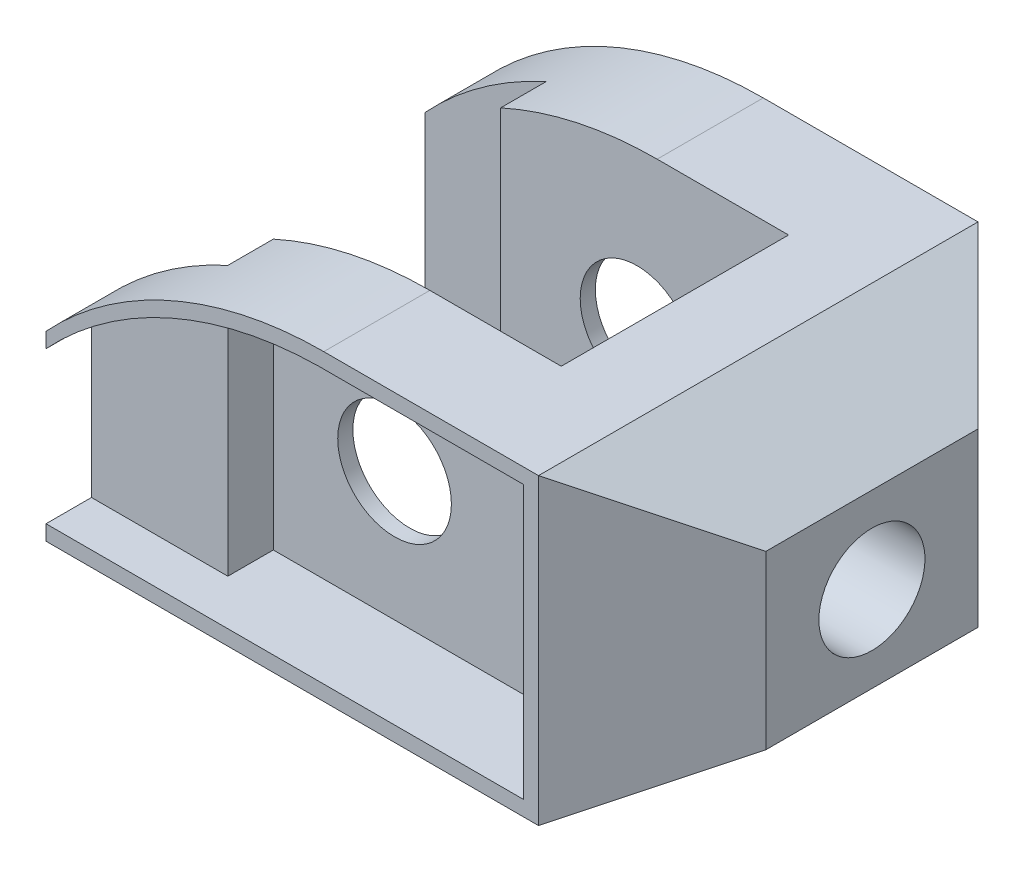
SolidWorks part; units mm, degrees
material "1060 Alloy"
ref_plane "Front Plane" through (0, 0, 0) normal (0, 0, 1) x (1, 0, 0)
ref_plane "Top Plane" through (0, 0, 0) normal (0, 1, 0) x (1, 0, 0)
ref_plane "Right Plane" through (0, 0, 0) normal (1, 0, 0) x (0, 0, -1)
sketch "Sketch2" plane through (0, 0, 0) normal (0, 1, 0) x (1, 0, 0)
  line L0 (0, 71.5823) -> (0, -71.5823) construction
  line L1 (-112.3291, 0) -> (112.3291, 0) construction
  line L3 (-40, 29) -> (40, 29)
  line L4 (-40, 29) -> (-40, -29)
  line L5 (-40, -29) -> (40, -29)
  line L6 (40, 29) -> (40, -29)
  point P0 (0, 0)
  point P4 (0, 0)
  point P8 (0, 0)
  dimension "D1" = 58
  dimension "D2" = 80
extrude "Boss-Extrude1" add sketch "Sketch2" along normal blind 40
sketch "Sketch4" plane through (0, 0, 0) normal (0, 0, 1) x (1, 0, 0)
  line L0 (40, 0) -> (25, 0)
  line L1 (-40, 0) -> (40, 0) construction
  line L2 (25, 0) -> (40, 8.6603)
  line L3 (40, 40) -> (40, 0) construction
  line L4 (40, 40) -> (25, 40)
  line L5 (-40, 40) -> (40, 40) construction
  line L6 (25, 40) -> (40, 31.3397)
  line L7 (-40, 0) -> (-40, 24)
  line L8 (-40, 40) -> (-40, 0) construction
  line L9 (25, 40) -> (-6, 40)
  line L10 (-6, 40) -> (-40, 40)
  line L11 (-40, 40) -> (-40, 24)
  line L12 (40, 40) -> (40, 0)
  line L13 (-40, 0) -> (40, 0)
  circle A0 centre (-6, 19) radius 7.5
  arc A2 (-3.3394, 40) -> (-40, 24) centre (-3.3394, -10) ccw
  dimension "D1" = 15
  dimension "D9" = 100
  dimension "D2" = 19
  dimension "D3" = 46
  dimension "D4" = 30
  dimension "D5" = 15
  dimension "D6" = 15
  dimension "D7" = 30
  dimension "D8" = 24
  dimension "D10" = 31
extrude "Cut-Extrude7" cut sketch "Sketch4" against normal blind 58 and the other way blind 58 contours A2 L9 L10 L11 | L12 L4 L6 | A0 | L12 L2 L0 region at (35, 2.8868, 0) region at (35, 37.1132, 0) region at (-31.154, 35.3681, 0) region at (-6, 19, 0)
sketch "Sketch12" plane through (0, 40, 0) normal (0, 1, 0) x (1, 0, 0)
  line L0 (14, 29) -> (14, -29)
  line L1 (25, 29) -> (-3.3394, 29) construction
  line L2 (-3.3394, -29) -> (25, -29) construction
  line L3 (25, -29) -> (25, 29) construction
  line L4 (14, 15) -> (-40, 15)
  line L5 (-40, -29) -> (-40, 29) construction
  line L6 (14, -15) -> (-40, -15)
  line L7 (-3.3394, 29) -> (-40, 29) construction
  line L8 (-40, -29) -> (-3.3394, -29) construction
  line L9 (-40, 15) -> (-40, 29)
  line L10 (-40, 29) -> (14, 29)
  line L11 (-40, -15) -> (-40, -29)
  line L12 (-40, -29) -> (14, -29)
  line L13 (-40, 15) -> (-40, -15)
  line L14 (-40, 15) -> (-40, -15)
  line M4 (-3.3394, 29) -> (-3.3394, -29)
  dimension "D1" = 11
  dimension "D2" = 14
  dimension "D3" = 14
extrude "Cut-Extrude10" cut sketch "Sketch12" against normal blind 58 contours L4 L13 L6 M4 | L6 L0 L4 M4 region at (5.3303, 40, 0) region at (-21.6697, 40, 0)
sketch "Sketch14" plane through (0, 40, 0) normal (0, 1, 0) x (1, 0, 0)
  line L0 (-3.3394, 29) -> (-40, 29) construction
  line L1 (-40, 15) -> (-24, 15)
  line L2 (-40, 15) -> (-40, 21)
  line L3 (-40, 21) -> (-24, 21)
  line L4 (-24, 15) -> (-24, 21)
  line L5 (-40, -29) -> (-3.3394, -29) construction
  line L6 (-40, -15) -> (-24, -15)
  line L7 (-40, -15) -> (-40, -21)
  line L8 (-40, -21) -> (-24, -21)
  line L9 (-24, -15) -> (-24, -21)
  dimension "D1" = 16
  dimension "D2" = 6
  dimension "D3" = 8
  dimension "D4" = 16
  dimension "D5" = 6
  dimension "D6" = 8
extrude "Cut-Extrude11" cut sketch "Sketch14" against normal blind 58 and the other way blind 58
sketch "Sketch17" plane through (40, 0, 0) normal (1, 0, 0) x (0, 0, -1)
  circle A0 centre (0, 20) radius 7
  dimension "D1" = 14
  dimension "D2" = 29
  dimension "D3" = 20
extrude "Cut-Extrude12" cut sketch "Sketch17" against normal blind 58 and the other way blind 58
sketch "Sketch19" plane through (0, 40, 0) normal (0, 1, 0) x (1, 0, 0)
  line L0 (25, 29) -> (40, 29)
  line L3 (40, -29) -> (40, 29) construction
  line L4 (25, 29) -> (40, 14)
  line L5 (40, 14) -> (40, 29)
  line L8 (25, -29) -> (40, -14)
  line L9 (40, -14) -> (40, -29)
  line L10 (40, -29) -> (25, -29)
  point P8 (14, 15)
  point P14 (14, -15)
  dimension "D1" = 45
  dimension "D2" = 45
extrude "Cut-Extrude14" cut sketch "Sketch19" against normal blind 58 and the other way blind 58
sketch "Sketch20" plane through (0, 0, 29) normal (0, 0, 1) x (1, 0, 0)
  line L0 (23, 38) -> (23, 2)
  line L1 (23, 2) -> (-40, 2)
  line L2 (-40, 24) -> (-40, 0) construction
  line L3 (23, 38) -> (-4, 38)
  line L4 (-40, 2) -> (-40, 22)
  line L5 (-3.3394, 40) -> (25, 40) construction
  line L6 (25, 40) -> (25, 0) construction
  line L7 (-40, 0) -> (25, 0) construction
  line L9 (-22, 34.3901) -> (-22, 2)
  arc A0 (-4, 38) -> (-40, 22) centre (-3.3353, -11.9956) ccw
  circle M1 centre (-6, 19) radius 7.5
  dimension "D5" = 100
  dimension "D7" = 18
  dimension "D1" = 2
  dimension "D2" = 2
  dimension "D3" = 2
  dimension "D4" = 2
  dimension "D6" = 18
extrude "Cut-Extrude15" cut sketch "Sketch20" against normal blind 12 contours L3 A0 L9 L1 L0 M1 region at (1.586, 19.8615, 29)
sketch "Sketch22" plane through (0, 0, 29) normal (0, 0, 1) x (1, 0, 0)
  line L0 (-22, 2) -> (-40, 2)
  line L1 (-40, 24) -> (-40, 0) construction
  line L2 (-40, 2) -> (-40, 22)
  line L3 (-40, 0) -> (25, 0) construction
  line L4 (-22, 2) -> (-22, 34.3901)
  arc A1 (-22, 34.3901) -> (-40, 22) centre (-3.3353, -11.9956) ccw
  dimension "D3" = 100
  dimension "D1" = 2
  dimension "D2" = 2
extrude "Cut-Extrude16" cut sketch "Sketch22" against normal blind 6
sketch "Sketch23" plane through (0, 0, -29) normal (0, 0, -1) x (-1, 0, 0)
  line L0 (-23, 38) -> (-23, 2)
  line L1 (-23, 2) -> (40, 2)
  line L3 (-23, 38) -> (4, 38)
  line L4 (-25, 40) -> (-25, 0) construction
  line L5 (-25, 0) -> (40, 0) construction
  line L6 (-25, 40) -> (3.3394, 40) construction
  line L7 (22, 34.3901) -> (22, 2)
  line L8 (40, 24) -> (40, 0) construction
  line L9 (40, 2) -> (40, 22)
  arc A0 (40, 22) -> (4, 38) centre (3.3353, -11.9956) ccw
  circle M1 centre (6, 19) radius 7.5
  dimension "D5" = 100
  dimension "D1" = 2
  dimension "D2" = 2
  dimension "D3" = 2
  dimension "D4" = 2
  dimension "D6" = 18
  dimension "D7" = 18
extrude "Cut-Extrude17" cut sketch "Sketch23" against normal blind 12 contours L7 A0 L3 L0 L1 M1 region at (1.586, 19.8615, -29)
sketch "Sketch24" plane through (0, 0, -29) normal (0, 0, -1) x (-1, 0, 0)
  line L0 (22, 2) -> (40, 2)
  line L1 (40, 24) -> (40, 0) construction
  line L2 (40, 2) -> (40, 22)
  line L3 (22, 2) -> (22, 34.3901)
  arc A0 (40, 22) -> (22, 34.3901) centre (3.3353, -11.9956) ccw
  dimension "D2" = 100
  dimension "D1" = 2
extrude "Cut-Extrude18" cut sketch "Sketch24" against normal blind 6
